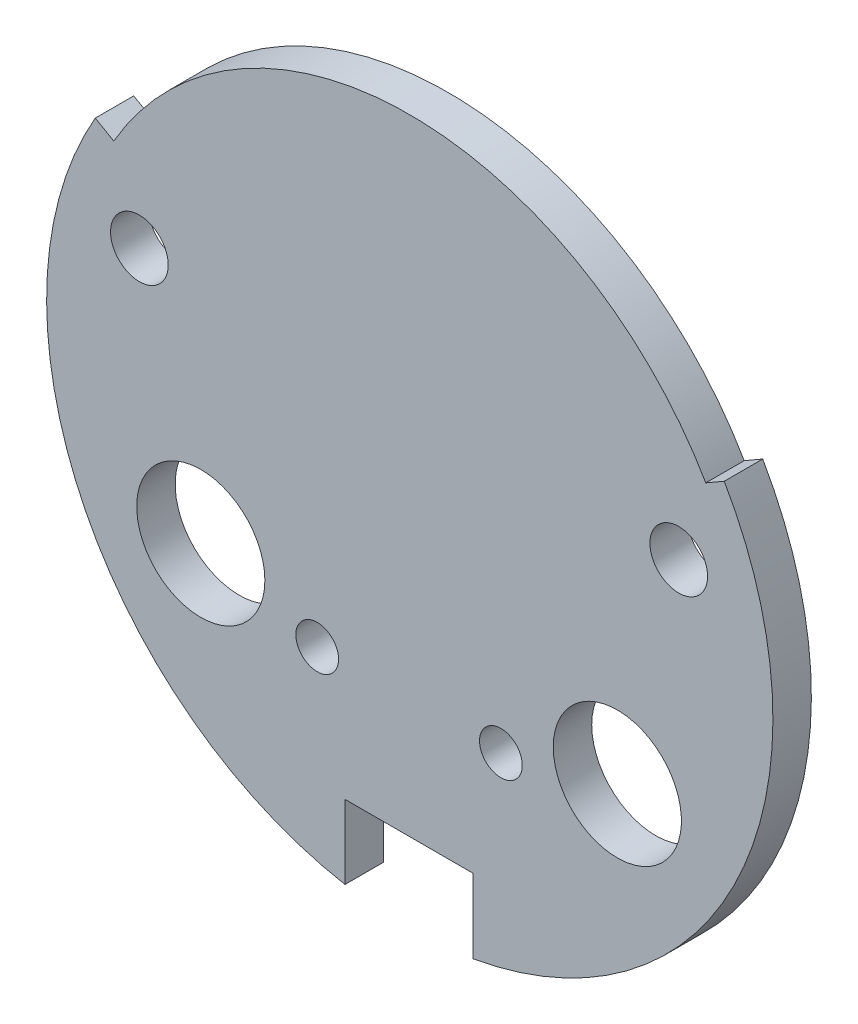
SolidWorks part; units mm, degrees
ref_plane "Front Plane" through (0, 0, 0) normal (0, 0, 1) x (1, 0, 0)
ref_plane "Top Plane" through (0, 0, 0) normal (0, 1, 0) x (1, 0, 0)
ref_plane "Right Plane" through (0, 0, 0) normal (1, 0, 0) x (0, 0, -1)
sketch "Sketch1" plane through (0, 0, 0) normal (0, 0, 1) x (1, 0, 0)
  line L0 (-3.3523, -12.4645) -> (2.6477, -12.4645)
  line L1 (-3.3523, -12.4645) -> (-3.3523, -15.9167)
  line L2 (2.6477, -12.4645) -> (2.6477, -15.9287)
  line L3 (-14.1754, 8.8105) -> (-15.0415, 9.3105)
  line L7 (14.4034, 9.3105) -> (13.5374, 8.8105)
  arc A1 (13.5374, 8.8105) -> (-14.1754, 8.8105) centre (-0.319, 0.8105) ccw
  arc A2 (-15.0415, 9.3105) -> (-3.3523, -15.9167) centre (-0.319, 0.8105) ccw
  arc A3 (2.6477, -15.9287) -> (14.4034, 9.3105) centre (-0.319, 0.8105) ccw
  point P3 (-0.3523, -12.4645)
  dimension "D1" = 17
  dimension "D2" = 16
  dimension "D3" = 1
  dimension "D4" = 1
  dimension "D5" = 6
  dimension "D6" = 13.275
extrude "Boss-Extrude1" add sketch "Sketch1" along normal blind 1.8
sketch "Sketch2" plane through (0, 0, 1.8) normal (0, 0, 1) x (1, 0, 0)
  line L0 (-23.4253, -5.4645) -> (23.8274, -5.4645) construction
  line L1 (-3.3523, -12.4645) -> (2.6477, -12.4645) construction
  line L2 (-0.3523, -12.4645) -> (-0.3523, 9.3801) construction
  circle A0 centre (-10.1023, -5.4645) radius 3
  circle A1 centre (9.3977, -5.4645) radius 3
  circle A2 centre (-12.9773, 5.0605) radius 1.35
  circle A3 centre (12.2727, 5.0605) radius 1.35
  circle A4 centre (-4.6523, -6.9395) radius 1
  circle A5 centre (3.9477, -6.9395) radius 1
  dimension "D2" = 6
  dimension "D3" = 9.75
  dimension "D4" = 2.7
  dimension "D5" = 10.525
  dimension "D6" = 12.625
  dimension "D7" = 1.475
  dimension "D8" = 2
  dimension "D9" = 4.3
  dimension "D1" = 7
extrude "Cut-Extrude1" cut sketch "Sketch2" against normal through all
